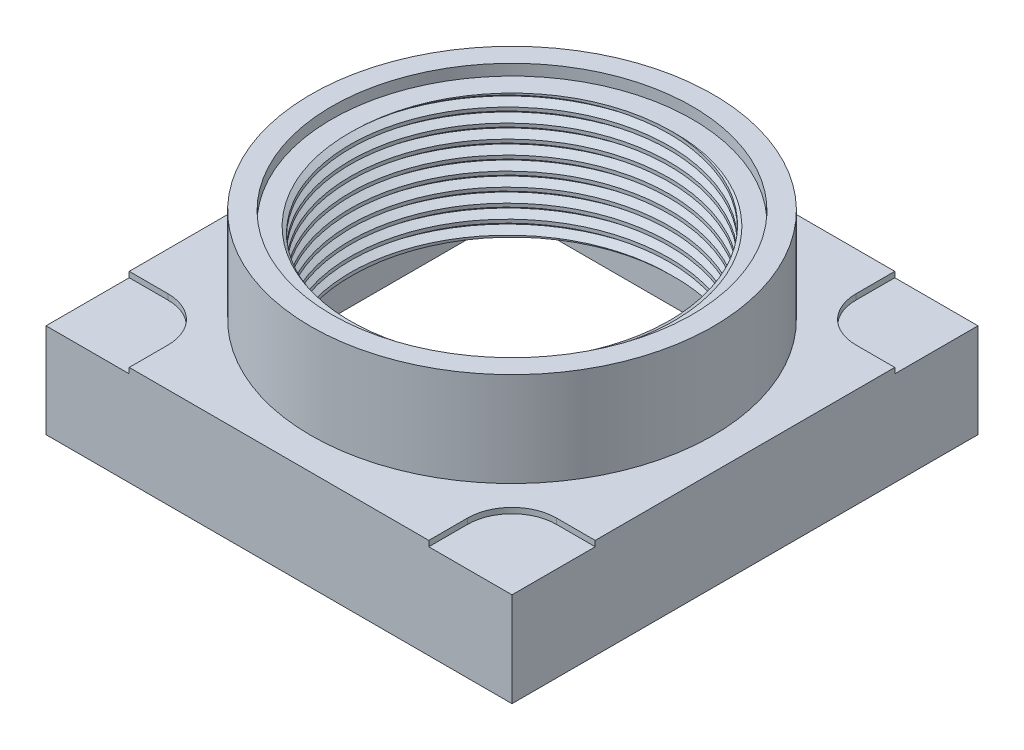
SolidWorks part; units mm, degrees
ref_plane "Front Plane" through (0, 0, 0) normal (0, 0, 1) x (1, 0, 0)
ref_plane "Top Plane" through (0, 0, 0) normal (0, 1, 0) x (1, 0, 0)
ref_plane "Right Plane" through (0, 0, 0) normal (1, 0, 0) x (0, 0, -1)
sketch "Sketch1" plane through (0, 0, 0) normal (0, 1, 0) x (1, 0, 0)
  line L1 (-4.2, 4.2) -> (4.2, 4.2)
  line L2 (-4.2, 4.2) -> (-4.2, -4.2)
  line L3 (-4.2, -4.2) -> (4.2, -4.2)
  line L4 (4.2, 4.2) -> (4.2, -4.2)
  line L5 (-4.2, 4.2) -> (4.2, -4.2) construction
  line L6 (-4.2, -4.2) -> (4.2, 4.2) construction
  point P0 (0, 0)
  dimension "D1" = 8.4
extrude "Boss-Extrude1" add sketch "Sketch1" along normal blind 1.8
sketch "Sketch2" plane through (0, 1.8, 0) normal (0, 1, 0) x (1, 0, 0)
  circle A0 centre (0, 0) radius 3.625
  dimension "D1" = 7.25
extrude "Boss-Extrude2" add sketch "Sketch2" along normal blind 1.7
shell "Shell1" thickness 0.75 removed face at (0, 0, 0)
sketch "Sketch3" plane through (0, 2.75, 0) normal (0, -1, 0) x (1, 0, 0)
  circle A1 centre (0, 0) radius 2.875
  circle A2 centre (0, 0) radius 2.875
  dimension "D1" = 0
extrude "Cut-Extrude1" cut sketch "Sketch3" against normal through all
sketch "Sketch4" plane through (0, 3.5, 0) normal (0, 1, 0) x (1, 0, 0)
  line L0 (0, 3.625) -> (0, 2.875) construction
  circle A0 centre (0, 0) radius 3.625 construction
  circle A1 centre (0, 0) radius 3.625 construction
  circle A2 centre (0, 0) radius 2.875 construction
  circle A3 centre (0, 0) radius 2.875
  circle A4 centre (0, 0) radius 3.25
  point P9 (0, 3.25)
extrude "Cut-Extrude2" cut sketch "Sketch4" against normal blind 0.2
sketch "Sketch5" plane through (0, 1.8, 0) normal (0, 1, 0) x (1, 0, 0)
  line L0 (0, 4.2) -> (0, -4.2) construction
  line L1 (-4.2, 4.2) -> (-2.7, 4.2)
  line L2 (-4.2, 4.2) -> (-4.2, 2.7)
  line L3 (-4.2, 2.7) -> (-3.5, 2.7)
  line L4 (-2.7, 4.2) -> (-2.7, 3.5)
  line L5 (4.2, 4.2) -> (-4.2, 4.2) construction
  line L6 (-4.2, -4.2) -> (4.2, -4.2) construction
  line L7 (-4.2, 0) -> (4.2, 0) construction
  line L8 (-4.2, 4.2) -> (-4.2, -4.2) construction
  line L9 (4.2, -4.2) -> (4.2, 4.2) construction
  line L10 (4.2, 2.7) -> (3.5, 2.7)
  line L11 (2.7, 4.2) -> (2.7, 3.5)
  line L12 (4.2, 4.2) -> (2.7, 4.2)
  line L13 (4.2, 4.2) -> (4.2, 2.7)
  line L14 (4.2, -4.2) -> (4.2, -2.7)
  line L15 (4.2, -4.2) -> (2.7, -4.2)
  line L16 (2.7, -4.2) -> (2.7, -3.5)
  line L17 (4.2, -2.7) -> (3.5, -2.7)
  line L18 (-4.2, -2.7) -> (-3.5, -2.7)
  line L19 (-2.7, -4.2) -> (-2.7, -3.5)
  line L20 (-4.2, -4.2) -> (-2.7, -4.2)
  line L21 (-4.2, -4.2) -> (-4.2, -2.7)
  arc A0 (-3.5, 2.7) -> (-2.7, 3.5) centre (-3.5, 3.5) ccw
  arc A1 (3.5, 2.7) -> (2.7, 3.5) centre (3.5, 3.5) cw
  arc A2 (3.5, -2.7) -> (2.7, -3.5) centre (3.5, -3.5) ccw
  arc A3 (-3.5, -2.7) -> (-2.7, -3.5) centre (-3.5, -3.5) cw
  dimension "D2" = 0.8
  dimension "D1" = 1.5
extrude "Cut-Extrude3" cut sketch "Sketch5" against normal blind 0.1
thread "Thread1" pitch 0.25 method cut profile "Thread Profile1" start angle 0, offset 0.5, length 3, pitch 0.25, diameter 5.75
ref_plane "Plane1" through (-2.875, 3.8, 0) normal (0, 0, 1) x (-1, 0, 0)
sketch "Thread Profile1" plane through (-2.875, 3.8, 0) normal (0, 0, 1) x (-1, 0, 0)
  line L0 (0, 0) -> (0, 0.25) construction
  line L1 (0, 0) -> (0.1353, 0.0781)
  line L2 (0.1353, 0.0781) -> (0.1353, 0.1094)
  line L3 (0.1353, 0.1094) -> (0, 0.1875)
  line L4 (0.1353, 0.0937) -> (0, 0.0937) construction
  line L11 (0, 0) -> (0, 0.1875)
  point P2 (0, 0)
  dimension "Pitch" = 0.25
  dimension "Profile_Angle" = 60
  dimension "Profile_Land" = 0.0312
  dimension "Profile_Height" = 0.1353
